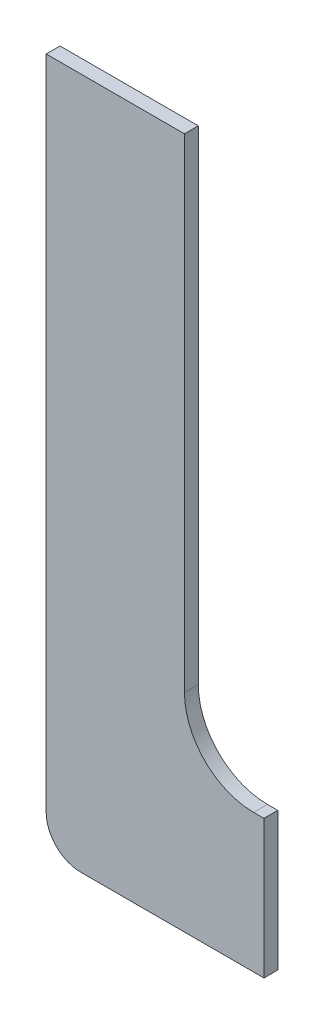
SolidWorks part; units mm, degrees
ref_plane "前视基准面" through (0, 0, 0) normal (0, 0, 1) x (1, 0, 0)
ref_plane "上视基准面" through (0, 0, 0) normal (0, 1, 0) x (1, 0, 0)
ref_plane "右视基准面" through (0, 0, 0) normal (1, 0, 0) x (0, 0, -1)
sketch "草图1" plane through (0, 0, 0) normal (0, 0, 1) x (1, 0, 0)
  line L0 (0, 0) -> (-31.5, 0)
  line L1 (-31.5, 0) -> (-31.5, 100)
  line L2 (-31.5, 100) -> (-11.5, 100)
  line L3 (-11.5, 100) -> (-11.5, 20)
  line L4 (-11.5, 20) -> (0, 20)
  line L5 (0, 20) -> (0, 0)
  dimension "D1" = 100
  dimension "D2" = 31.5
  dimension "D3" = 20
  dimension "D4" = 20
extrude "凸台-拉伸1" add sketch "草图1" along normal blind 2
fillet "圆角1" radius 10 1 edges at (-11.5, 20, 1)
fillet "圆角2" radius 5 1 edges at (-31.5, 0, 1)
sketch3d "3D草图1"
  line L0 (-11.5, 30, 2) -> (-11.5, 100, 2) construction
  arc A0 (-1.5, 20, 2) -> (-11.5, 30, 2) centre (-1.5, 30, 2) ccw construction
  point P0 (-1.5, 20, 2)
  point P1 (-8.5711, 22.9289, 2)
  point P3 (-11.5, 30, 2)
  point P7 (-1.5, 30, -8)
  point P8 (-11.5, 49.1552, 2)
  point P10 (-11.5, 87.2694, 2)
  point P13 (0, 0, 0)
  point P14 (0, 0, 0)
  point P15 (0, 0, 0)
  point P16 (0, 0, 0)
  point P17 (0, 0, 0)
  point P18 (0, 0, 0)
  point P19 (0, 0, 0)
  point P20 (0, 0, 0)
  point P21 (0, 0, 0)
